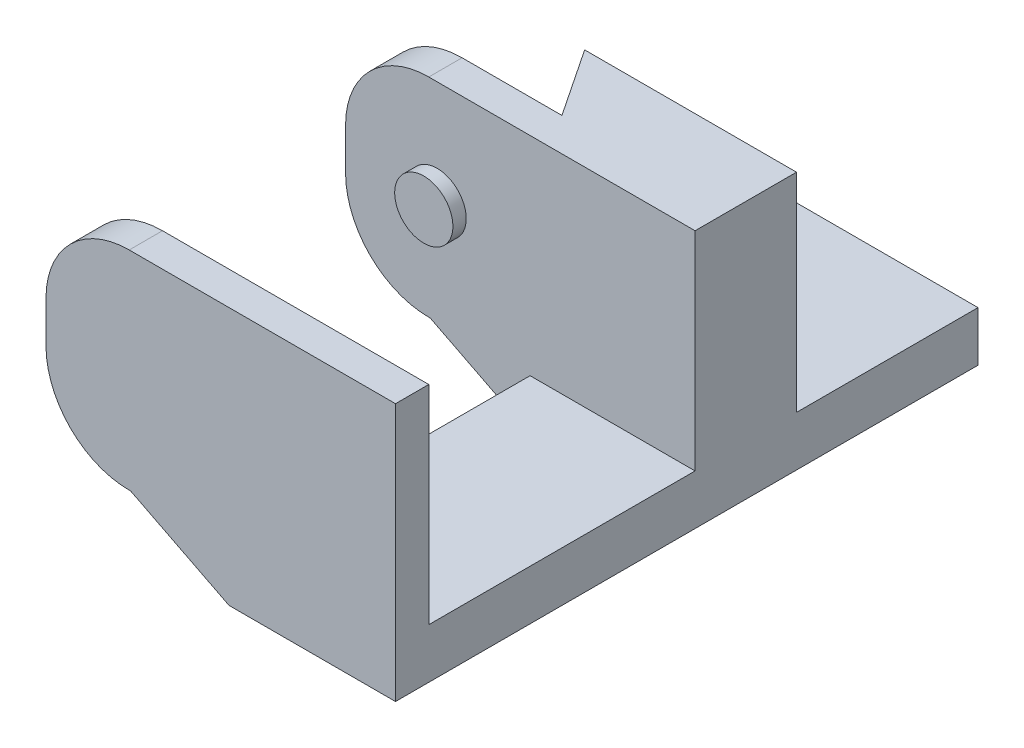
SolidWorks part; units mm, degrees
ref_plane "Plano frontal" through (0, 0, 0) normal (0, 0, 1) x (1, 0, 0)
ref_plane "Plano superior" through (0, 0, 0) normal (0, 1, 0) x (1, 0, 0)
ref_plane "Plano direito" through (0, 0, 0) normal (1, 0, 0) x (0, 0, -1)
sketch "Esboço1" plane through (0, 0, 0) normal (0, 1, 0) x (1, 0, 0)
  line L0 (-6.3766, 5) -> (-6.3766, -0.4351)
  line L1 (-3.3333, -5) -> (10, -5)
  line L3 (-6.3766, 5) -> (10, 5)
  line L4 (10, -5) -> (10, 5)
  line L5 (-5, -2.5) -> (10, 5) construction
  line L6 (-6.3766, 3.1883) -> (10, -5) construction
  line L7 (-3.3333, -5) -> (10, -5)
  line L9 (0, -30) -> (10, -30)
  line L10 (10, -5) -> (10, -12)
  line L11 (-3.3333, -5) -> (10, -5)
  line L13 (0, -10) -> (-6.3766, -0.4351)
  line L14 (10, -5) -> (10, -10)
  line L15 (10, -10) -> (10, -30)
  line L17 (5, -10) -> (0, -10)
  line L18 (10, -10) -> (10, -12)
  line L21 (0, -30) -> (0, -10)
  line L22 (10, -30) -> (10, -28)
  line L25 (5, -10) -> (10, -10)
  line L26 (10, -30) -> (10, -10)
  line L27 (10, -12) -> (10, -10)
  line L28 (0, -30) -> (0, -28)
  line L29 (0, -28) -> (10, -28)
  line L30 (10, -30) -> (10, -28)
  line L31 (0, -10) -> (10, -10)
  line L32 (0, -10) -> (0, -12)
  line L33 (0, -12) -> (10, -12)
  line L34 (10, -10) -> (10, -12)
  circle A0 centre (1.8117, -0.9059) radius 2
  point P0 (0, 0)
  dimension "D7" = 4
  dimension "D1" = 10
  dimension "D3" = 25
  dimension "D6" = 2
  dimension "D8" = 2
  dimension "D9" = 20
extrude "Ressalto-extrusão1" add sketch "Esboço1" along normal blind 3 contours L1 L4 L3 A0 | L10 L1 | L10 | L10 | L10 | L33 L21 L29 | L29 L21 | L33 L29 L26 | L21 L33 L17 region at (1.8117, 0, -4.8081) region at (4.127, 0, 7.381) region at (5, 0, 11) region at (5, 0, 20) region at (5, 0, 29)
extrude "Ressalto-extrusão5" add sketch "Esboço1<4>" along normal blind 15.5 contours L29 L21 L10 | L21 L33 L10 L25 L17 region at (5, 0, 11) region at (5, 0, 29)
sketch "Esboço1<4>" plane through (0, 0, 0) normal (0, 1, 0) x (1, 0, 0) same geometry as "Esboço1"
sketch "Esboço8" plane through (10, 0, 0) normal (1, 0, 0) x (0, 0, -1)
  line L1 (-28, 15.5) -> (-12, 15.5)
  line L2 (-28, 15.5) -> (-28, 3)
  line L3 (-28, 3) -> (-12, 3)
  line L4 (-12, 15.5) -> (-12, 3)
  line L5 (-27.2, 15.5) -> (-12.8, 15.5)
  line L6 (-27.2, 15.5) -> (-27.2, 3)
  line L7 (-27.2, 3) -> (-12.8, 3)
  line L8 (-12.8, 15.5) -> (-12.8, 3)
  dimension "D1" = 0.8
  dimension "D2" = 0.8
sketch "Esboço10" plane through (0, 3, 0) normal (0, 1, 0) x (1, 0, 0)
  line L0 (1.8117, -0.9059) -> (1.8117, -5.9059)
  line L1 (10, -10) -> (10, 5) construction
  line L2 (0, -10) -> (10, -10)
  line L4 (0, -5.9059) -> (10, -5.9059)
  line L5 (10, -10) -> (10, -5.9059)
  line L6 (0, -5.9059) -> (-2.7294, -5.9059)
  line L7 (0, -10) -> (-6.3766, -0.4351) construction
  line L8 (-2.7294, -5.9059) -> (0, -10)
  line M2 (0, -10) -> (10, -10)
  line M3 (10, -10) -> (10, 5)
  line M6 (-6.3766, -0.4351) -> (0, -10)
  dimension "D1" = 5
extrude "Ressalto-extrusão6" add sketch "Esboço10" along normal up to surface (12.5 mm away) contours L4 L6 M6 M2 M3 region at (4.2903, 3, 7.871) up to face at (5, 15.5, 11)
sketch "Esboço11" plane through (0, 0, 0) normal (-1, 0, 0) x (0, 0, 1)
  line L1 (12, 3) -> (10, 3)
  line L2 (12, 3) -> (12, 15.5)
  line L3 (12, 15.5) -> (10, 15.5)
  line L4 (10, 3) -> (10, 15.5)
  line L5 (28, 3) -> (30, 3)
  line L6 (28, 3) -> (28, 15.5)
  line L7 (28, 15.5) -> (30, 15.5)
  line L8 (30, 3) -> (30, 15.5)
extrude "Ressalto-extrusão7" add sketch "Esboço11" along normal blind 11
sketch "Esboço12" plane through (0, 0, 30) normal (0, 0, 1) x (1, 0, 0)
  line L0 (-11, 3) -> (0, 15.5)
  line L1 (-11, 15.5) -> (10, 15.5) construction
  line L2 (-11, 15.5) -> (0, 3)
  circle A0 centre (-5.5, 9.25) radius 1.75
  dimension "D1" = 3.5
extrude "Ressalto-extrusão8" add sketch "Esboço12" against normal up to surface (18 mm away) contours L2 A0 L0 | L0 A0 L2 | L0 A0 L2 | L2 A0 L0 region at (-6.5314, 9.25, 30) region at (-5.5, 8.182, 30) region at (-5.5, 10.318, 30) region at (-4.4686, 9.25, 30) up to face at (-0.4, 8, 12)
extrude "Corte-extrusão1" cut sketch "Esboço8" against normal through all contours L8 L1 L6 L3 region at (10, 9.25, 20)
fillet "Filete1" radius 5 4 edges at (-11, 3, 11) (-11, 15.5, 11) (-11, 15.5, 29) (-11, 3, 29)
ref_plane "Plano1" through (0, 3, 28) normal (0, 0, 1) x (1, 0, 0)
sketch "Esboço14" plane through (0, 3, 28) normal (0, 0, 1) x (1, 0, 0)
  line L0 (-6, 5) -> (0, -3)
  line L1 (0, -3) -> (0, 0)
  line L2 (0, 0) -> (-5.9132, 0)
  line L3 (-5.9132, 0) -> (0, -3)
extrude "Ressalto-extrusão9" add sketch "Esboço14" along normal blind 2 and the other way blind 18 contours L2 L3 L0 | L1 L2 L0 region at (-0.75, 2, 28) region at (-2.7211, 2, 28)
sketch "Esboço18" plane through (0, 3, 0) normal (0, 1, 0) x (1, 0, 0)
  line L1 (-5.9132, -12) -> (0.0868, -12)
  line L2 (-5.9132, -12) -> (-5.9132, -28)
  line L3 (-5.9132, -28) -> (0.0868, -28)
  line L4 (0.0868, -12) -> (0.0868, -28)
  dimension "D1" = 6
extrude "Corte-extrusão3" cut sketch "Esboço18" against normal through all
